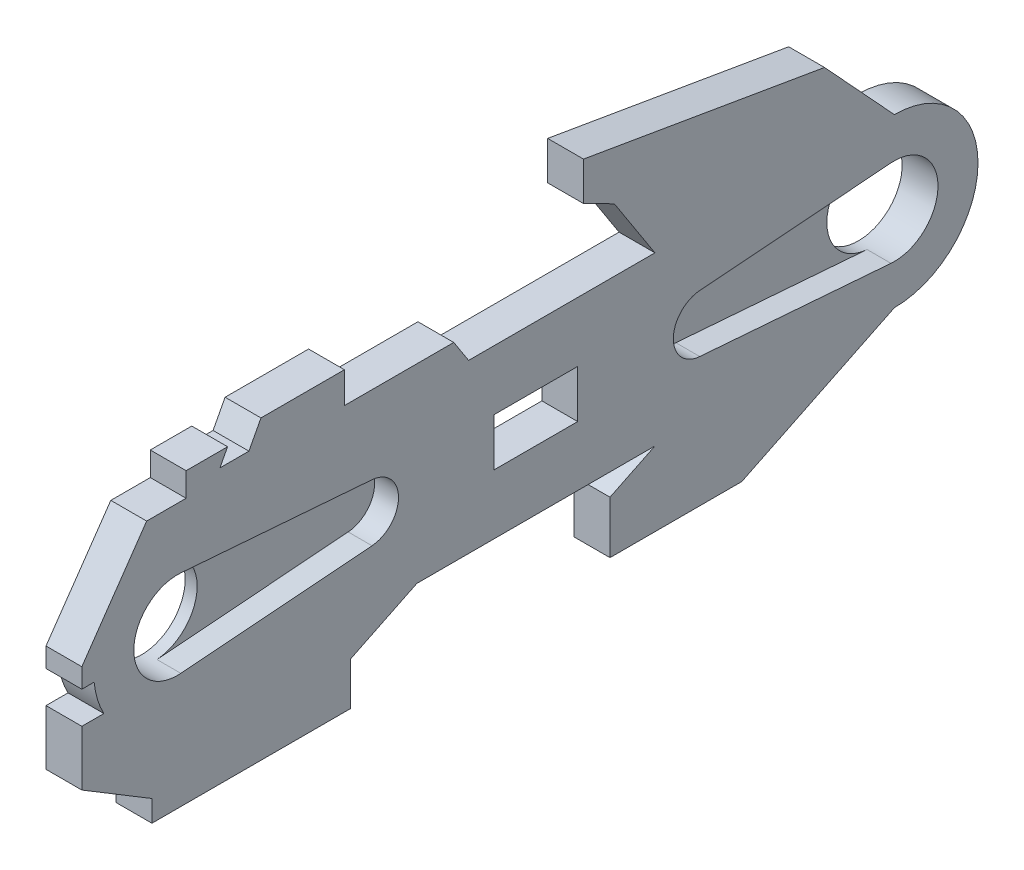
SolidWorks part; units mm, degrees
ref_plane "Front Plane" through (0, 0, 0) normal (0, 0, 1) x (1, 0, 0)
ref_plane "Top Plane" through (0, 0, 0) normal (0, 1, 0) x (1, 0, 0)
ref_plane "Right Plane" through (0, 0, 0) normal (1, 0, 0) x (0, 0, -1)
sketch "Sketch2" plane through (0, 0, 0) normal (0, 1, 0) x (1, 0, 0)
  line L0 (0, 0) -> (12, 0) construction
  line L1 (12, 30) -> (12, -30)
  line L2 (12, -30) -> (9, -30)
  line L3 (9, -30) -> (9, -1.5)
  line L4 (9, -1.5) -> (-9, -1.5)
  line L5 (0, 1.5) -> (0, -1.5) construction
  line L6 (-9, -30) -> (-9, -1.5)
  line L7 (-12, -30) -> (-9, -30)
  line L8 (-12, 30) -> (-12, -30)
  line L9 (-12, 30) -> (-9, 30)
  line L10 (-9, 30) -> (-9, 1.5)
  line L11 (9, 1.5) -> (-9, 1.5)
  line L12 (9, 30) -> (9, 1.5)
  line L13 (12, 30) -> (9, 30)
  point P13 (-12, 0)
  dimension "D1" = 3
  dimension "D2" = 3
  dimension "D3" = 30
extrude "Boss-Extrude1" add sketch "Sketch2" along normal blind 7 and the other way blind 7
sketch "Sketch3" plane through (12, 0, 0) normal (1, 0, 0) x (0, 0, -1)
  line L0 (-30, -7) -> (-30, 7) construction
  line L1 (30, -7) -> (30, 7) construction
  circle A0 centre (-30, 0) radius 7
  circle A1 centre (30, 0) radius 7
extrude "Boss-Extrude2" add sketch "Sketch3" against normal blind 3
ref_plane "Plane1" through (0, 0, 0) normal (-1, 0, 0) x (0, 0, 1)
mirror "Mirror1" about plane through (0, 0, 0) normal (-1, 0, 0) of "Boss-Extrude2"
sketch "Sketch4" plane through (0, 0, 0) normal (-1, 0, 0) x (0, 0, 1)
  circle A0 centre (-30, 0) radius 4
  circle A1 centre (30, 0) radius 4
extrude "Cut-Extrude1" cut sketch "Sketch4" against normal blind 23 and the other way blind 23
sketch "Sketch5" plane through (-12, 0, 0) normal (-1, 0, 0) x (0, 0, 1)
  line L0 (-30, 7) -> (-24.1554, 13.3392)
  line L4 (-6.564, 12.2529) -> (-9.9611, 7)
  line L5 (-30, 7) -> (30, 7) construction
  line L6 (5.6302, 7) -> (6.8729, 8.9217)
  line L7 (6.8729, 8.9217) -> (16.0243, 8.9217)
  line L8 (16.0243, 8.9217) -> (16.0243, 11.5202)
  line L9 (16.0243, 11.5202) -> (23.0108, 11.5202)
  line L10 (23.0108, 11.5202) -> (24.0174, 9.6146)
  line L11 (24.0174, 9.6146) -> (26.4427, 9.6146)
  line L12 (26.4427, 9.6146) -> (25.8021, 10.8273)
  line L13 (25.8021, 10.8273) -> (33.6254, 10.8273)
  line L14 (33.6254, 10.8273) -> (39.5845, 2.2088)
  line L15 (39.5845, 2.2088) -> (39.5845, -0.6496)
  line L16 (39.5845, -0.6496) -> (35.4504, -0.6496)
  line L17 (35.4504, -0.6496) -> (35.4504, 3.2482)
  line L18 (35.4504, 3.2482) -> (30.5617, 6.4097)
  line L19 (30.5617, 6.4097) -> (5.6302, 6.4097)
  line L20 (5.6302, 6.4097) -> (5.6302, 7)
  line L21 (-30, 7) -> (-9.9611, 7)
  line L22 (-30, -7) -> (-17.2297, -13.2151)
  line L23 (-17.2297, -13.2151) -> (-6.201, -13.2151)
  line L24 (-6.201, -13.2151) -> (-6.201, -8.83)
  line L25 (-6.201, -8.83) -> (-9.9611, -7)
  line L26 (-30, -7) -> (30, -7) construction
  line L27 (-9.9611, -7) -> (-30, -7)
  line L28 (9.9611, -7) -> (15.5248, -9.7078)
  line L29 (15.5248, -9.7078) -> (15.5248, -13.2959)
  line L30 (15.5248, -13.2959) -> (32.1353, -13.2959)
  line L31 (32.1353, -13.2959) -> (32.1353, -11.5018)
  line L32 (32.1353, -11.5018) -> (39.5845, -7)
  line L33 (39.5845, -7) -> (39.5845, -3.3348)
  line L34 (39.5845, -3.3348) -> (35.4504, -3.3348)
  line L35 (35.4504, -3.3348) -> (31.745, -5.5741)
  line L36 (31.745, -5.5741) -> (9.9611, -5.5741)
  line L37 (9.9611, -5.5741) -> (9.9611, -7)
  line L38 (-24.1554, 13.3392) -> (-3.9844, 16.7822)
  line L39 (-3.9844, 16.7822) -> (-3.9844, 13.5584)
  line L40 (-3.9844, 13.5584) -> (-6.564, 12.2529)
extrude "Boss-Extrude3" add sketch "Sketch5" against normal blind 3
mirror "Mirror2" about plane through (0, 0, 0) normal (-1, 0, 0) of "Boss-Extrude3"
sketch "Sketch6" plane through (0, 7, 0) normal (0, 1, 0) x (1, 0, 0)
  line L1 (-9, 37) -> (27.1461, 37)
  line L2 (-9, 37) -> (-9, -42.8814)
  line L3 (-9, -42.8814) -> (27.1461, -42.8814)
  line L4 (27.1461, 37) -> (27.1461, -42.8814)
extrude "Cut-Extrude2" cut sketch "Sketch6" against normal blind 30 and the other way blind 20
sketch "Sketch7" plane through (-12, 0, 0) normal (-1, 0, 0) x (0, 0, 1)
  line L0 (-3, -1) -> (-3, -3)
  line L3 (-3, -1) -> (3, -1)
  line L5 (0, 0) -> (3, -1) construction
  line L6 (-3, -1) -> (0, 0) construction
  line L7 (-3, -3) -> (3, -3)
  line L8 (3, -3) -> (3, -1)
  point P0 (0, 0)
extrude "Boss-Extrude4" add sketch "Sketch7" along normal blind 25
sketch "Sketch8" plane through (0, -1, 0) normal (0, 1, 0) x (1, 0, 0)
  line L0 (-12, -3) -> (-12, 3) construction
  circle A0 centre (-34, 0) radius 1.5
  circle A1 centre (-26, 0) radius 1.5
  dimension "D1" = 22
  dimension "D2" = 14
extrude "Cut-Extrude3" cut sketch "Sketch8" against normal blind 25
sketch "Sketch9" plane through (-12, 0, 0) normal (-1, 0, 0) x (0, 0, 1)
  line L1 (-3, -1) -> (3, -1)
  line L2 (-3, -1) -> (-3, 1)
  line L3 (-3, 1) -> (3, 1)
  line L4 (3, -1) -> (3, 1)
extrude "Boss-Extrude5" add sketch "Sketch9" along normal blind 11
sketch "Sketch10" plane through (-9, 0, 0) normal (1, 0, 0) x (0, 0, -1)
  circle A0 centre (-30, 0) radius 4
  circle A1 centre (30, 0) radius 4
  circle A2 centre (-30, 0) radius 3.65
  circle A3 centre (30, 0) radius 3.65
  dimension "D1" = 7.3
  dimension "D2" = 7.3
extrude "Boss-Extrude7" add sketch "Sketch10" against normal up to surface (3 mm away) up to face at (-12, 1.3496, 11.5835)
sketch "Sketch11" plane through (-9, 0, 0) normal (1, 0, 0) x (0, 0, -1)
  line L0 (-29.7166, 3.639) -> (-13.7137, 2.3928)
  line L1 (-29.7166, -3.639) -> (-13.7137, -2.3928)
  line L2 (13.7137, 2.3928) -> (29.7166, 3.639)
  line L3 (13.7137, -2.3928) -> (29.7166, -3.639)
  circle A1 centre (-30, 0) radius 3.65
  circle A2 centre (30, 0) radius 3.65
  circle A3 centre (13.9, 0) radius 2.4
  circle A4 centre (-13.9, 0) radius 2.4
  circle M34 centre (-30, 0) radius 3.65
  circle M35 centre (30, 0) radius 3.65
  dimension "D1" = 7.3
  dimension "D2" = 7.3
  dimension "D3" = 4.8
  dimension "D4" = 4.8
  dimension "D5" = 16.1
  dimension "D6" = 16.1
extrude "Cut-Extrude4" cut sketch "Sketch11" against normal up to surface (3 mm away) contours A4 L0 L1 M34 | A4 | A3 L3 L2 M35 | A3 region at (-9, 0, 21.68) region at (-9, 0, 13.9) region at (-9, 0, -21.68) region at (-9, 0, -13.9) up to face at (-12, 1.3496, 11.5835)
sketch "Sketch13" plane through (-12, 0, 0) normal (-1, 0, 0) x (0, 0, 1)
  line L1 (-34.1168, 4.4773) -> (35.0877, 4.4773)
  line L2 (-34.1168, 4.4773) -> (-34.1168, -4.8456)
  line L3 (-34.1168, -4.8456) -> (35.0877, -4.8456)
  line L4 (35.0877, 4.4773) -> (35.0877, -4.8456)
  circle A0 centre (-30, 0) radius 3.65
  circle A1 centre (30, 0) radius 3.65
extrude "Boss-Extrude9" add sketch "Sketch13" against normal blind 1
sketch "Sketch14" plane through (-9, 0, 0) normal (1, 0, 0) x (0, 0, -1)
  line L1 (-49.1158, 21.2406) -> (-38, 21.2406)
  line L2 (-49.1158, 21.2406) -> (-49.1158, -22.6846)
  line L3 (-49.1158, -22.6846) -> (-38, -22.6846)
  line L4 (-38, 21.2406) -> (-38, -22.6846)
  dimension "D1" = 38
extrude "Cut-Extrude5" cut sketch "Sketch14" against normal blind 31
sketch "Sketch15" plane through (-9, 0, 0) normal (1, 0, 0) x (0, 0, -1)
  line L0 (-39.3002, -0.8968) -> (-32.5767, 8.8273)
  line L1 (-32.5767, 8.8273) -> (-29.2731, 8.8273)
  line L2 (-29.2731, 8.8273) -> (-29.2731, 11.0159)
  line L3 (-29.2731, 11.0159) -> (-39.3002, 11.0159)
  line L4 (-39.3002, 11.0159) -> (-39.3002, -0.8968)
  line L5 (-38, 4.5003) -> (-33.6254, 10.8273) construction
  line L7 (-33.6254, 10.8273) -> (-25.8021, 10.8273) construction
  dimension "D1" = 2
  dimension "D2" = 2
extrude "Cut-Extrude6" cut sketch "Sketch15" against normal blind 22
sketch "Sketch16" plane through (0, 1, 0) normal (0, 1, 0) x (1, 0, 0)
  line L1 (-12, -3) -> (-42.4401, -3)
  line L2 (-12, -3) -> (-12, 5.4465)
  line L3 (-12, 5.4465) -> (-42.4401, 5.4465)
  line L4 (-42.4401, -3) -> (-42.4401, 5.4465)
extrude "Cut-Extrude7" cut sketch "Sketch16" against normal blind 10
sketch "Sketch17" plane through (-12, 0, 0) normal (-1, 0, 0) x (0, 0, 1)
  line L1 (-3.5, 2) -> (3.5, 2)
  line L2 (-3.5, 2) -> (-3.5, -2)
  line L3 (-3.5, -2) -> (3.5, -2)
  line L4 (3.5, 2) -> (3.5, -2)
  line L5 (-3.5, 2) -> (3.5, -2) construction
  line L6 (-3.5, -2) -> (3.5, 2) construction
  point P0 (0, 0)
extrude "Cut-Extrude8" cut sketch "Sketch17" against normal blind 10
